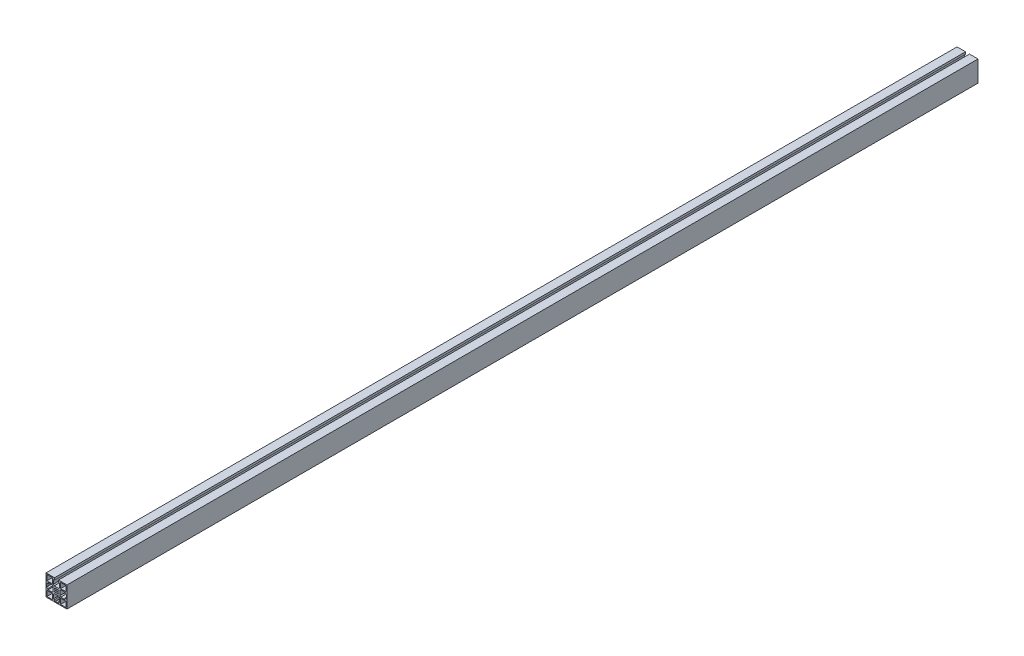
SolidWorks part; units mm, degrees
material "6061 Alloy"
ref_plane "Front Plane" through (0, 0, 0) normal (0, 0, 1) x (1, 0, 0)
ref_plane "Top Plane" through (0, 0, 0) normal (0, 1, 0) x (1, 0, 0)
ref_plane "Right Plane" through (0, 0, 0) normal (1, 0, 0) x (0, 0, -1)
sketch "Sketch1" plane through (0, 0, 0) normal (0, 0, 1) x (1, 0, 0)
  line L0 (-4.2495, 22.1993) -> (-4.2495, 22.4993)
  line L1 (-4.2495, 22.4993) -> (-4.2495, 22.1993)
  line L2 (4.2505, 22.1993) -> (4.2505, 22.4993)
  line L3 (4.2505, 22.4993) -> (4.2505, 22.1993)
  line L8 (-22.4995, -22.5007) -> (22.5005, -22.5007)
  line L9 (22.5005, -22.5007) -> (22.5005, 22.4993)
  line L10 (22.5005, 22.4993) -> (-22.4995, 22.4993)
  line L11 (-22.4995, 22.4993) -> (-22.4995, -22.5007)
  line L24 (-20.4995, -20.5007) -> (-20.4995, -8.8007)
  line L25 (-8.7996, -20.5007) -> (-20.4995, -20.5007)
  line L26 (-8.7996, -8.8007) -> (-8.7996, -20.5007)
  line L27 (-20.4995, -8.8007) -> (-8.7996, -8.8007)
  line L28 (8.8005, -20.5008) -> (8.8005, -8.8008)
  line L29 (20.5005, -20.5008) -> (8.8005, -20.5008)
  line L30 (20.5005, -8.8008) -> (20.5005, -20.5008)
  line L31 (8.8005, -8.8008) -> (20.5005, -8.8008)
  line L32 (20.5006, 8.7993) -> (8.8006, 8.7993)
  line L33 (20.5006, 20.4993) -> (20.5006, 8.7993)
  line L34 (8.8006, 20.4993) -> (20.5006, 20.4993)
  line L35 (8.8006, 8.7993) -> (8.8006, 20.4993)
  line L36 (-8.7995, 20.4993) -> (-8.7995, 8.7993)
  line L37 (-8.7995, 8.7993) -> (-20.4995, 8.7993)
  line L38 (-20.4995, 8.7993) -> (-20.4995, 20.4993)
  line L39 (-20.4995, 20.4993) -> (-8.7995, 20.4993)
  line L54 (-22.1995, -3.9507) -> (-21.7318, -3.483)
  line L55 (-22.1995, -4.2507) -> (-22.1995, -3.9507)
  line L56 (-17.9995, -4.2507) -> (-22.1995, -4.2507)
  line L57 (-17.9995, -6.8007) -> (-17.9995, -4.2507)
  line L58 (-9.1995, -6.8007) -> (-17.9995, -6.8007)
  line L59 (-7.1995, -4.8007) -> (-9.1995, -6.8007)
  line L60 (-7.1995, 4.7993) -> (-7.1995, -4.8007)
  line L61 (-9.1995, 6.7993) -> (-7.1995, 4.7993)
  line L62 (-17.9995, 6.7993) -> (-9.1995, 6.7993)
  line L63 (-17.9995, 4.2493) -> (-17.9995, 6.7993)
  line L64 (-22.1995, 4.2493) -> (-17.9995, 4.2493)
  line L65 (-22.1995, 3.9493) -> (-22.1995, 4.2493)
  line L66 (-21.7317, 3.4815) -> (-22.1995, 3.9493)
  line L67 (-20.9995, -1.7152) -> (-20.9995, 1.7137)
  line L82 (-6.7995, -18.0007) -> (-6.7995, -9.2007)
  line L83 (-4.2495, -18.0007) -> (-6.7995, -18.0007)
  line L84 (-4.2495, -22.2007) -> (-4.2495, -18.0007)
  line L85 (-3.9495, -22.2007) -> (-4.2495, -22.2007)
  line L86 (-3.4817, -21.733) -> (-3.9495, -22.2007)
  line L87 (1.715, -21.0007) -> (-1.7139, -21.0007)
  line L88 (3.9505, -22.2007) -> (3.4828, -21.733)
  line L89 (4.2505, -22.2007) -> (3.9505, -22.2007)
  line L90 (4.2505, -18.0007) -> (4.2505, -22.2007)
  line L91 (6.8005, -18.0007) -> (4.2505, -18.0007)
  line L92 (6.8005, -9.2007) -> (6.8005, -18.0007)
  line L93 (4.8005, -7.2007) -> (6.8005, -9.2007)
  line L94 (-4.7995, -7.2007) -> (4.8005, -7.2007)
  line L95 (-6.7995, -9.2007) -> (-4.7995, -7.2007)
  line L110 (7.2005, -4.8007) -> (7.2005, 4.7993)
  line L111 (9.2005, -6.8007) -> (7.2005, -4.8007)
  line L112 (18.0005, -6.8007) -> (9.2005, -6.8007)
  line L113 (18.0005, -4.2507) -> (18.0005, -6.8007)
  line L114 (22.2005, -4.2507) -> (18.0005, -4.2507)
  line L115 (22.2005, -3.9507) -> (22.2005, -4.2507)
  line L116 (21.7327, -3.4829) -> (22.2005, -3.9507)
  line L117 (21.0005, 1.7138) -> (21.0005, -1.7151)
  line L118 (22.2005, 3.9493) -> (21.7328, 3.4816)
  line L119 (22.2005, 4.2493) -> (22.2005, 3.9493)
  line L120 (18.0005, 4.2493) -> (22.2005, 4.2493)
  line L121 (18.0005, 6.7993) -> (18.0005, 4.2493)
  line L122 (9.2005, 6.7993) -> (18.0005, 6.7993)
  line L123 (7.2005, 4.7993) -> (9.2005, 6.7993)
  line L138 (-4.7995, 7.1993) -> (-6.7995, 9.1993)
  line L139 (4.8005, 7.1993) -> (-4.7995, 7.1993)
  line L140 (6.8005, 9.1993) -> (4.8005, 7.1993)
  line L141 (6.8005, 17.9993) -> (6.8005, 9.1993)
  line L142 (4.2505, 17.9993) -> (6.8005, 17.9993)
  line L143 (4.2505, 22.1993) -> (4.2505, 17.9993)
  line L144 (3.9505, 22.1993) -> (4.2505, 22.1993)
  line L145 (3.4828, 21.7316) -> (3.9505, 22.1993)
  line L146 (-1.7139, 20.9993) -> (1.715, 20.9993)
  line L147 (-3.9495, 22.1993) -> (-3.4817, 21.7315)
  line L148 (-4.2495, 22.1993) -> (-3.9495, 22.1993)
  line L149 (-4.2495, 17.9993) -> (-4.2495, 22.1993)
  line L150 (-6.7995, 17.9993) -> (-4.2495, 17.9993)
  line L151 (-6.7995, 9.1993) -> (-6.7995, 17.9993)
  line L164 (-4.5957, -3.1827) -> (-3.2622, -1.8492)
  line L165 (-3.1815, -4.5969) -> (-4.5957, -3.1827)
  line L166 (-1.848, -3.2635) -> (-3.1815, -4.5969)
  line L167 (3.1825, -4.5969) -> (1.849, -3.2635)
  line L168 (4.5967, -3.1827) -> (3.1825, -4.5969)
  line L169 (3.2633, -1.8492) -> (4.5967, -3.1827)
  line L170 (4.5967, 3.1813) -> (3.2633, 1.8478)
  line L171 (3.1825, 4.5955) -> (4.5967, 3.1813)
  line L172 (1.849, 3.262) -> (3.1825, 4.5955)
  line L173 (-3.1815, 4.5955) -> (-1.848, 3.262)
  line L174 (-4.5957, 3.1813) -> (-3.1815, 4.5955)
  line L175 (-3.2622, 1.8478) -> (-4.5957, 3.1813)
  arc A2 (-21.7318, -3.483) -> (-20.9995, -1.7152) centre (-23.4995, -1.7152) ccw
  arc A3 (-20.9995, 1.7137) -> (-21.7317, 3.4815) centre (-23.4995, 1.7137) ccw
  arc A6 (-1.7139, -21.0007) -> (-3.4817, -21.733) centre (-1.7139, -23.5007) ccw
  arc A7 (3.4828, -21.733) -> (1.715, -21.0007) centre (1.715, -23.5007) ccw
  arc A10 (21.0005, -1.7151) -> (21.7327, -3.4829) centre (23.5005, -1.7151) ccw
  arc A11 (21.7328, 3.4816) -> (21.0005, 1.7138) centre (23.5005, 1.7138) ccw
  arc A14 (1.715, 20.9993) -> (3.4828, 21.7316) centre (1.715, 23.4993) ccw
  arc A15 (-3.4817, 21.7315) -> (-1.7139, 20.9993) centre (-1.7139, 23.4993) ccw
  arc A20 (-1.848, -3.2635) -> (1.849, -3.2635) centre (0.0005, -0.0007) ccw
  arc A21 (3.2633, -1.8492) -> (3.2633, 1.8478) centre (0.0005, -0.0007) ccw
  arc A22 (1.849, 3.262) -> (-1.848, 3.262) centre (0.0005, -0.0007) ccw
  arc A23 (-3.2622, 1.8478) -> (-3.2622, -1.8492) centre (0.0005, -0.0007) ccw
extrude "Boss-Extrude1" add sketch "Sketch1" along normal blind 1955.8 contours L10 L11 L8 L9 A23 L175 L174 L173 A22 L172 L171 L170 A21 L169 L168 L167 A20 L166 L165 L164 L24 L27 L26 L25 L28 L31 L30 L29 L32 L35 L34 L33 L38 L39 L36 L37 L67 A3 L66 L65 L64 L63 L62 L61 L60 region at (-4.8859, 20.0993, 0)
